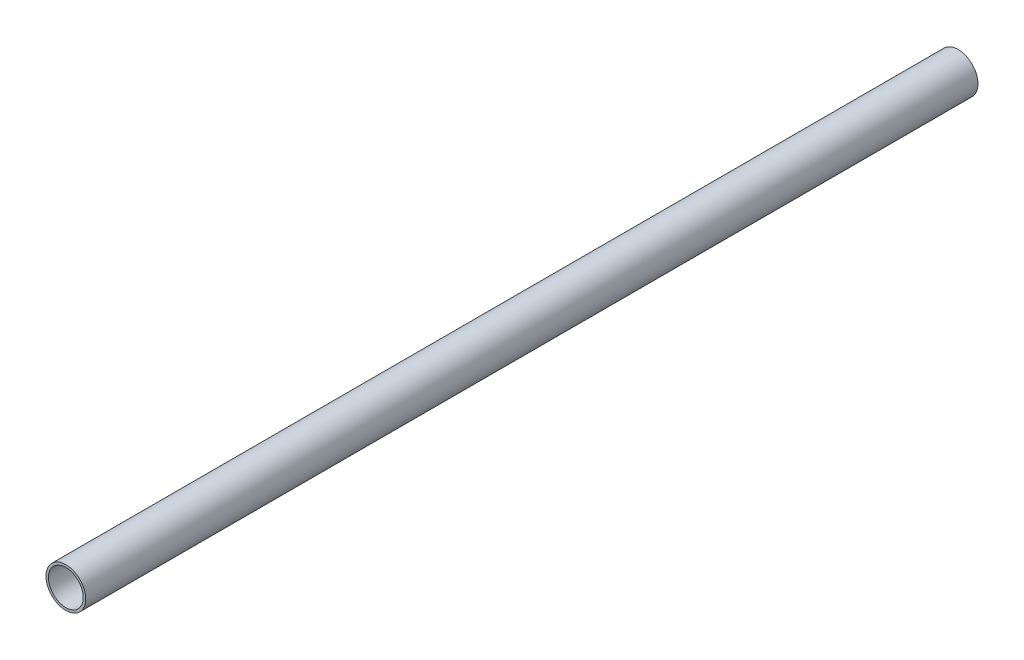
SolidWorks part; units mm, degrees
material "PC High Viscosity"
ref_plane "Front Plane" through (0, 0, 0) normal (0, 0, 1) x (1, 0, 0)
ref_plane "Top Plane" through (0, 0, 0) normal (0, 1, 0) x (1, 0, 0)
ref_plane "Right Plane" through (0, 0, 0) normal (1, 0, 0) x (0, 0, -1)
sketch "Sketch2" plane through (0, 0, 0) normal (0, 0, 1) x (1, 0, 0)
  circle A0 centre (0, 0) radius 11.1125
  circle A1 centre (0, 0) radius 12.7
  dimension "D1" = 25.4
  dimension "D2" = 22.225
extrude "Boss-Extrude1" add sketch "Sketch2" along normal mid plane 570.1883
